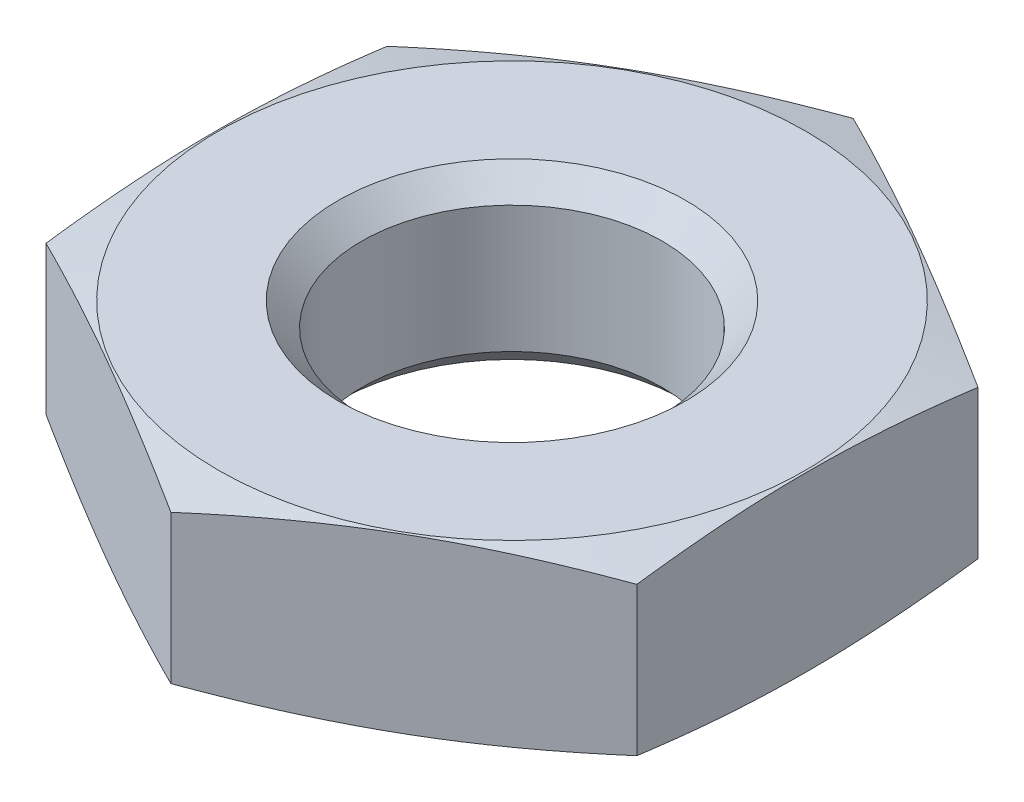
SolidWorks part; units mm, degrees
ref_plane "Front Plane" through (0, 0, 0) normal (0, 0, 1) x (1, 0, 0)
ref_plane "Top Plane" through (0, 0, 0) normal (0, 1, 0) x (1, 0, 0)
ref_plane "Right Plane" through (0, 0, 0) normal (1, 0, 0) x (0, 0, -1)
sketch "Sketch1" plane through (0, 0, 0) normal (0, 0, 1) x (1, 0, 0)
  line L0 (0, 0) -> (8.45, 0)
  line L1 (8.45, 0) -> (17.7801, -2.5)
  line L2 (17.7801, -2.5) -> (8.45, -5)
  line L3 (8.45, -5) -> (0, -5)
  line L4 (0, -5) -> (0, 0)
  line L5 (0, -5) -> (0, 0) construction
revolve "Revolve1" add sketch "Sketch1" angle 360 about L5
sketch "Sketch2" plane through (0, 0, 0) normal (0, 1, 0) x (1, 0, 0)
  line L0 (-34, 34) -> (-34, -34)
  line L1 (-34, -34) -> (34, -34)
  line L2 (34, -34) -> (34, 34)
  line L3 (34, 34) -> (-34, 34)
  line L4 (-8.5, -4.9075) -> (0, -9.815)
  line L5 (0, -9.815) -> (8.5, -4.9075)
  line L6 (8.5, -4.9075) -> (8.5, 4.9075)
  line L7 (8.5, 4.9075) -> (0, 9.815)
  line L8 (0, 9.815) -> (-8.5, 4.9075)
  line L9 (-8.5, 4.9075) -> (-8.5, -4.9075)
extrude "Cut-Extrude1" cut sketch "Sketch2" along normal blind 6 and the other way blind 6
sketch "Sketch3" plane through (0, 0, 0) normal (0, 0, 1) x (1, 0, 0)
  line L0 (0, 0) -> (5, 0)
  line L1 (5, 0) -> (4.3235, -0.6765)
  line L2 (4.3235, -0.6765) -> (4.3235, -4.3235)
  line L3 (4.3235, -4.3235) -> (5, -5)
  line L4 (5, -5) -> (0, -5)
  line L5 (0, -5) -> (0, 0)
  line L6 (0, -5) -> (0, 0) construction
revolve "Cut-Revolve1" cut sketch "Sketch3" angle 360 about L6 reverse direction yes
cosmetic thread "Cosmetic Thread1" parameters "D1"=5, "D2"=10
ref_plane "Plane4" through (0, -2.5, 0) normal (0, 1, 0) x (1, 0, 0)
ref_plane "2CYL XY" through (0, -2.5, 0) normal (0, 1, 0) x (1, 0, 0)
ref_plane "2CYL XZ" through (0, 0, 0) normal (0, 0, 1) x (1, 0, 0)
ref_plane "2CYL YZ" through (0, 0, 0) normal (1, 0, 0) x (0, 0, -1)
ref_axis "2CYL X" through (-80.9, -2.5, 0) along (1, 0, 0)
ref_axis "2CYL Y" through (0, -2.5, 50) along (0, 0, -1)
ref_axis "2CYL Z" through (0, 50, 0) along (0, -1, 0)
sketch3d "2CYL"
  point P0 (0, -2.5, 0)
ref_plane "din439b_punkt XY" through (0, 0, 0) normal (0, 1, 0) x (1, 0, 0)
ref_plane "din439b_punkt XZ" through (0, 0, 0) normal (0, 0, 1) x (1, 0, 0)
ref_plane "din439b_punkt YZ" through (0, 0, 0) normal (1, 0, 0) x (0, 0, -1)
ref_axis "din439b_punkt X" through (-80.9, 0, 0) along (1, 0, 0)
ref_axis "din439b_punkt Y" through (0, 0, 50) along (0, 0, -1)
ref_axis "din439b_punkt Z" through (0, 50, 0) along (0, -1, 0)
sketch3d "din439b_punkt"
  point P0 (0, 0, 0)
other "Freeze***"
